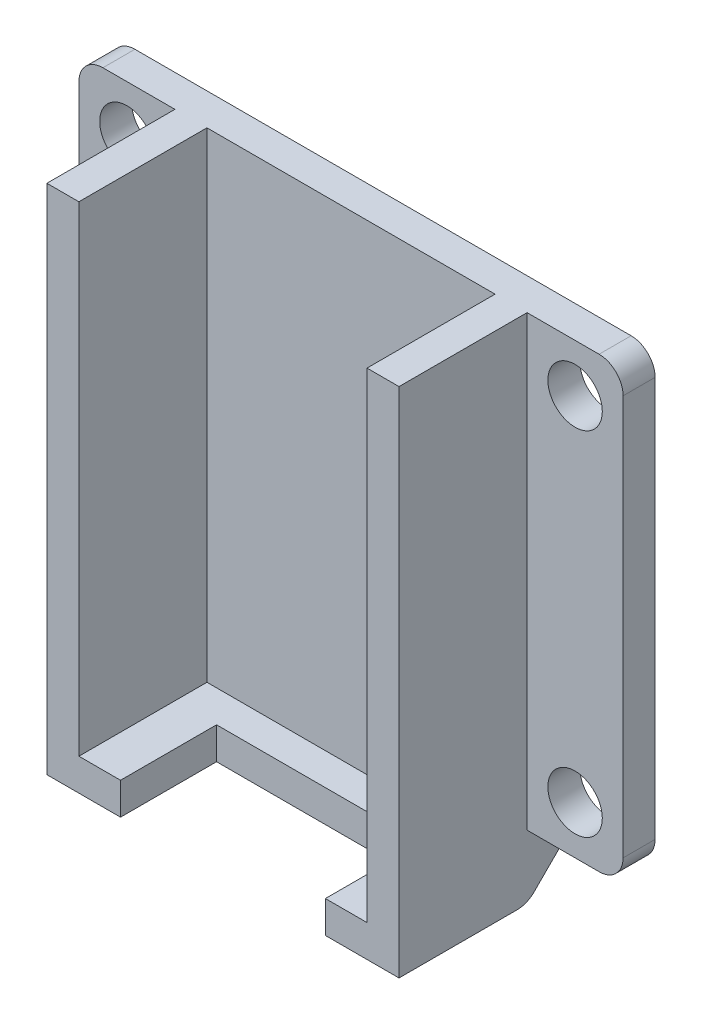
SolidWorks part; units mm, degrees
ref_plane "Front Plane" through (0, 0, 0) normal (0, 0, 1) x (1, 0, 0)
ref_plane "Top Plane" through (0, 0, 0) normal (0, 1, 0) x (1, 0, 0)
ref_plane "Right Plane" through (0, 0, 0) normal (1, 0, 0) x (0, 0, -1)
sketch "Sketch1" plane through (0, 0, 0) normal (0, 0, 1) x (1, 0, 0)
  line L1 (-17, -16) -> (17, -16)
  line L2 (-17, -16) -> (-17, 16)
  line L3 (-17, 16) -> (17, 16)
  line L4 (17, -16) -> (17, 16)
  line L5 (-17, -16) -> (17, 16) construction
  line L6 (-17, 16) -> (17, -16) construction
  point P0 (0, 0)
  dimension "D1" = 34
  dimension "D2" = 32
extrude "Boss-Extrude1" add sketch "Sketch1" along normal blind 2
sketch "Sketch2" plane through (0, 0, 2) normal (0, 0, 1) x (1, 0, 0)
  line L0 (17, 16) -> (-17, 16) construction
  line L1 (-11, 16) -> (-9, 16)
  line L2 (-11, 16) -> (-11, -16)
  line L3 (-11, -16) -> (-9, -16)
  line L4 (-9, 16) -> (-9, -16)
  line L5 (-17, -16) -> (17, -16) construction
  line L6 (-17, 16) -> (-17, -16) construction
  line L7 (11, 16) -> (9, 16)
  line L8 (11, 16) -> (11, -16)
  line L9 (11, -16) -> (9, -16)
  line L10 (9, 16) -> (9, -16)
  line L11 (-9, -14) -> (9, -14)
  line L12 (-9, -14) -> (-9, -16)
  line L13 (-9, -16) -> (9, -16)
  line L14 (9, -14) -> (9, -16)
  line L15 (17, -16) -> (17, 16) construction
  line L16 (0, -14) -> (0, -16) construction
  line L17 (-6.4, -14) -> (6.4, -14)
  line L18 (-6.4, -14) -> (-6.4, -16)
  line L19 (-6.4, -16) -> (6.4, -16)
  line L20 (6.4, -14) -> (6.4, -16)
  line L21 (0, -16) -> (0, -14) construction
  line M10 (17, 16) -> (-17, 16)
  line M12 (-17, -16) -> (17, -16)
  dimension "D1" = 2
  dimension "D2" = 2
  dimension "D3" = 2
  dimension "D4" = 6
  dimension "D5" = 6
  dimension "D6" = 12.8
extrude "Boss-Extrude2" add sketch "Sketch2" along normal blind 8 contours L10 L8 M10 M12 | L4 L2 M10 M12 | L18 L11 L4 M12 | L11 L20 L10 M12 region at (-10, 0, 2) region at (-7.7, -15, 2) region at (10, 0, 2) region at (7.7, -15, 2)
extrude "Boss-Extrude3" add sketch "Sketch2<4>" along normal blind 2 contours L20 L11 L18 L13 region at (0, -15, 2)
sketch "Sketch2<4>" plane through (0, 0, 2) normal (0, 0, 1) x (1, 0, 0) same geometry as "Sketch2"
sketch "Sketch3" plane through (0, 0, 2) normal (0, 0, 1) x (1, 0, 0)
  line L0 (-17, 16) -> (-17, -16) construction
  line L1 (-17, -16) -> (-11, -16)
  line L2 (-17, -16) -> (-17, -12)
  line L3 (-17, -12) -> (-11, -12)
  line L4 (-11, -16) -> (-11, -12)
  line L5 (-11, 16) -> (-11, -16) construction
  line L6 (-11, -16) -> (-6.4, -16) construction
  line L7 (11, -16) -> (17, -16) construction
  line L8 (17, -16) -> (11, -16)
  line L9 (17, -16) -> (17, -12)
  line L10 (17, -12) -> (11, -12)
  line L11 (11, -16) -> (11, -12)
  line L12 (11, 16) -> (11, -16) construction
  point P18 (17, -16)
  dimension "D1" = 4
  dimension "D2" = 4
extrude "Cut-Extrude1" cut sketch "Sketch3" against normal blind 9
sketch "Sketch4" plane through (0, 0, 2) normal (0, 0, 1) x (1, 0, 0)
  line L0 (17, -12) -> (11, -12) construction
  line L1 (-14, 13) -> (14, 13) construction
  line L2 (-14, 13) -> (-14, -9) construction
  line L3 (-14, -9) -> (14, -9) construction
  line L4 (14, 13) -> (14, -9) construction
  line L5 (17, -12) -> (17, 16) construction
  line L6 (-17, 16) -> (-17, -12) construction
  line L7 (-11, 16) -> (-17, 16) construction
  point P0 (-14, 13)
  point P1 (14, -9)
  point P2 (-14, -9)
  point P3 (14, 13)
  dimension "D1" = 3
  dimension "D2" = 3
  dimension "D3" = 3
  dimension "D4" = 3
hole_wizard "M3 Clearance Hole1" positions "Sketch4" profile "Sketch5" hole size "M3" standard "ANSI Metric"
sketch "Sketch5" plane through (-14, 13, 2) normal (1, 0, 0) x (0, -1, 0)
  line L0 (0, 0) -> (0, 11.0215)
  line L1 (0, 11.0215) -> (1.7, 10)
  line L2 (1.7, 10) -> (1.7, 0)
  line L5 (1.7, 0) -> (0, 0)
  line L10 (0, 11.0215) -> (-1.7, 10) construction
  line L11 (0, -6.35) -> (0, 107.95) construction
  dimension "Hole Dia." = 3.4
  dimension "Hole Depth" = 10
  dimension "Drill Angle" = 118
fillet "Fillet1" radius 1.5 4 edges at (-17, 16, 1) (17, 16, 1) (17, -12, 1) (-17, -12, 1)
chamfer "Chamfer1" distance 2 angle 45 1 edges at (0, -16, 0)
fillet "Fillet2" radius 1.5 1 edges at (0, -16, 2)
